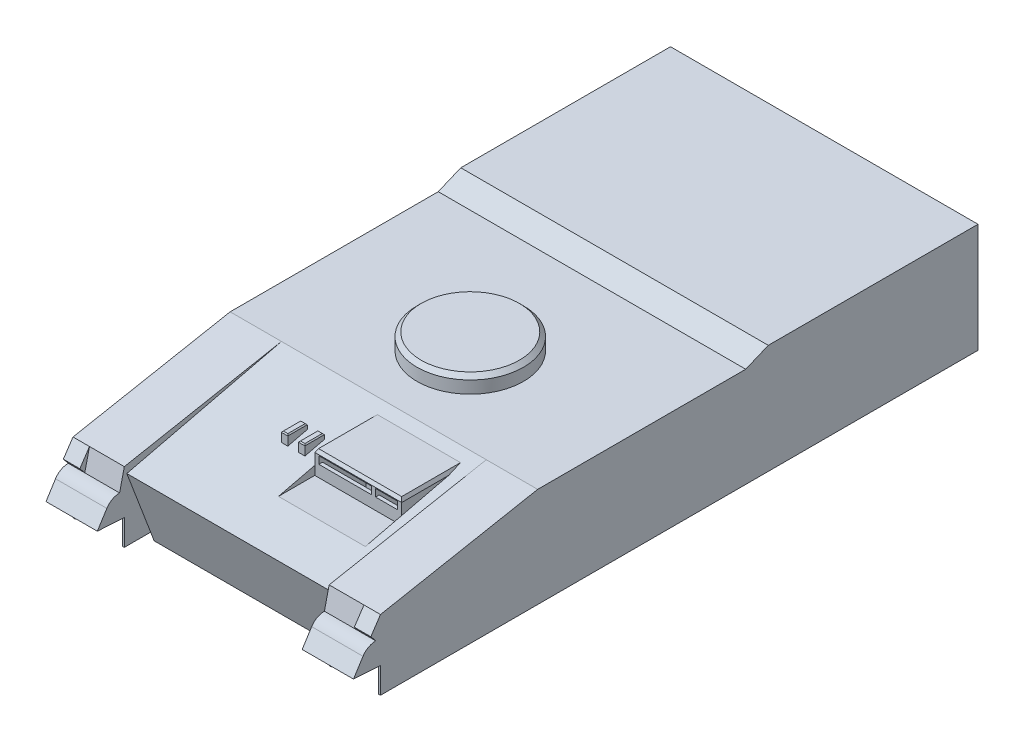
SolidWorks part; units mm, degrees
ref_plane "Front Plane" through (0, 0, 0) normal (0, 0, 1) x (1, 0, 0)
ref_plane "Top Plane" through (0, 0, 0) normal (0, 1, 0) x (1, 0, 0)
ref_plane "Right Plane" through (0, 0, 0) normal (1, 0, 0) x (0, 0, -1)
sketch "Sketch1" plane through (0, 0, 0) normal (0, 0, 1) x (1, 0, 0)
  line L1 (-266.9615, 243.5244) -> (483.6986, 243.5244)
  line L2 (-266.9615, 243.5244) -> (-266.9615, -106.3383)
  line L3 (-266.9615, -106.3383) -> (483.6986, -106.3383)
  line L4 (483.6986, 243.5244) -> (483.6986, -106.3383)
  point P0 (0, 0)
  dimension "D1" = 750.6601
extrude "Boss-Extrude1" add sketch "Sketch1" against normal blind 1265.04 and the other way blind 193.5622
ref_plane "Plane1" through (108.3686, 0, 0) normal (-1, 0, 0) x (0, 0, 1)
sketch "Sketch3" plane through (0, 243.5244, 0) normal (0, 1, 0) x (1, 0, 0)
  line L0 (148.6385, 524.5184) -> (483.6986, 524.5184)
  line L1 (-266.9615, 524.5184) -> (68.0986, 524.5184)
  line L2 (-266.9615, 1265.04) -> (-266.9615, -193.5622) construction
  line L3 (483.6986, 1265.04) -> (483.6986, -193.5622) construction
  circle A0 centre (108.3686, 400.9128) radius 130
  dimension "D1" = 260
extrude "Boss-Extrude2" add sketch "Sketch3" along normal blind 40 contours A0
sketch "Sketch5" plane through (483.6986, 0, 0) normal (1, 0, 0) x (0, 0, -1)
  line L0 (-193.5622, 170.7889) -> (190.0862, 243.5244)
  line L1 (-193.5622, -106.3383) -> (-193.5622, 243.5244) construction
  line L2 (-193.5622, 243.5244) -> (1265.04, 243.5244) construction
  line L3 (190.0862, 243.5244) -> (-193.5622, 243.5244)
  line L4 (-193.5622, 243.5244) -> (-193.5622, 170.7889)
  point P8 (94.4653, 243.5244)
  point P9 (-136.762, 199.7456)
  point P10 (-191.6549, 170.7889)
extrude "Cut-Extrude1" cut sketch "Sketch5" against normal through all
sketch "Sketch7" plane through (483.6986, 0, 0) normal (1, 0, 0) x (0, 0, -1)
  line L0 (698.0314, 243.5244) -> (753.11, 266.5226)
  line L1 (190.0862, 243.5244) -> (1265.04, 243.5244) construction
  line L2 (753.11, 266.5226) -> (1265.04, 266.5226)
  line L3 (1265.04, 243.5244) -> (1265.04, 266.5226)
  line L4 (698.0314, 243.5244) -> (1265.04, 243.5244)
  line L5 (190.0862, 243.5244) -> (1265.04, 243.5244) construction
  point P2 (694.3263, 267.5429)
  point P4 (0, 0)
  point P8 (837.0392, 270.0196)
  point P10 (769.721, 243.5244)
  point P13 (698.0314, 243.5244)
  point P14 (753.11, 266.5226)
extrude "Boss-Extrude3" add sketch "Sketch7" against normal up to surface (750.6601 mm away) up to face at (-266.9615, 89.0322, -466.6083)
chamfer "Chamfer7" distance 10 angle 45 1 edges at (108.3686, 283.5244, -270.9128)
sketch "Sketch21" plane through (-266.9615, 0, 0) normal (-1, 0, 0) x (0, 0, 1)
  line L1 (236.2193, 103.7623) -> (259.4333, 67.1114)
  line L2 (259.4333, 67.1114) -> (193.5622, 62.996)
  line L7 (193.5622, 62.996) -> (193.5622, 120.8855)
  line L8 (193.5622, 170.7889) -> (193.5622, -106.3383) construction
  line L10 (205.1048, 120.8855) -> (193.5622, 170.7889)
  line L11 (193.5622, 170.7889) -> (193.5622, 120.8855)
  arc A0 (205.1048, 120.8855) -> (236.2193, 103.7623) centre (205.1048, 84.0549) cw
  dimension "D1" = 36.8306
extrude "Boss-Extrude4" add sketch "Sketch21" against normal up to surface (750.6601 mm away) up to face at (483.6986, 139.7437, -540.5976)
sketch "Sketch20" plane through (-266.9615, 0, 0) normal (-1, 0, 0) x (0, 0, 1)
  line L0 (187.4855, 153.1852) -> (120.6339, -22.6923)
  line L1 (120.6339, -22.6923) -> (-169.8006, -69.1619)
  line L2 (193.5622, 170.7889) -> (316.2425, 170.7889)
  line L3 (-169.8006, -69.1619) -> (-1166.3691, -69.1619)
  line L4 (-1166.3691, -69.1619) -> (-1265.04, 144.9298)
  line L5 (-1265.04, 266.5226) -> (-1265.04, -106.3383) construction
  line L6 (-1265.04, 144.9298) -> (-1265.04, -106.3383)
  line L7 (-1265.04, -106.3383) -> (316.2425, -106.3383)
  line L8 (316.2425, -106.3383) -> (316.2425, 170.7889)
  line L9 (-190.0862, 243.5244) -> (187.4855, 153.1852)
  line L10 (-190.0862, 243.5244) -> (193.5622, 170.7889)
extrude "Cut-Extrude10" cut sketch "Sketch20" against normal mid plane 500 from surface at -375.3301
sketch "Sketch22" plane through (0, 0, 193.5622) normal (0, 0, 1) x (1, 0, 0)
  line L0 (-141.6314, 153.1852) -> (-141.6314, -22.6923) construction
  line L1 (-266.9615, -106.3383) -> (-141.6314, -106.3383)
  line L2 (-266.9615, -106.3383) -> (-266.9615, 0)
  line L3 (-266.9615, 0) -> (-141.6314, 0)
  line L4 (-141.6314, -106.3383) -> (-141.6314, 0)
  line L5 (-261.9615, 13.7359) -> (-266.9615, 13.7359)
  line L6 (-261.9615, 0) -> (-146.6314, 0)
  line L7 (-261.9615, 0) -> (-261.9615, 62.996)
  line L8 (-261.9615, 62.996) -> (-146.6314, 62.996)
  line L9 (-146.6314, 0) -> (-146.6314, 62.996)
  line L10 (-266.9615, 62.996) -> (-266.9615, -106.3383) construction
  line L11 (-141.6314, 62.996) -> (-266.9615, 62.996) construction
  line L13 (-146.6314, 20.3554) -> (-141.6314, 20.3554)
  line L14 (-141.6314, -106.3383) -> (-141.6314, 62.996) construction
  line L15 (108.3686, 192.4245) -> (108.3686, -192.4245) construction
  line L16 (363.3686, 20.3554) -> (358.3686, 20.3554)
  line L17 (363.3686, 0) -> (363.3686, 62.996)
  line L18 (478.6986, 62.996) -> (363.3686, 62.996)
  line L19 (478.6986, 0) -> (478.6986, 62.996)
  line L20 (478.6986, 0) -> (363.3686, 0)
  line L21 (478.6986, 13.7359) -> (483.6986, 13.7359)
  line L22 (358.3686, -106.3383) -> (358.3686, 0)
  line L23 (483.6986, 0) -> (358.3686, 0)
  line L24 (483.6986, -106.3383) -> (483.6986, 0)
  line L25 (483.6986, -106.3383) -> (358.3686, -106.3383)
  point P15 (-258.4833, 62.996)
  dimension "D1" = 5
extrude "Cut-Extrude11" cut sketch "Sketch22" against normal through all contours L3 L2 L9 | L3 L9 L8 L7 | L25 L24 L23 L20 L22 | L20 L19 L18 L17
sketch "Sketch24" plane through (0, 62.996, 0) normal (0, -1, 0) x (1, 0, 0)
  line L0 (-146.6314, -1265.04) -> (-261.9615, -1265.04) construction
  line L1 (-261.9615, 188.5622) -> (-146.6314, 188.5622)
  line L2 (-261.9615, 188.5622) -> (-261.9615, -69.9724)
  line L3 (-261.9615, -69.9724) -> (-146.6314, -69.9724)
  line L4 (-146.6314, 188.5622) -> (-146.6314, -69.9724)
  line L7 (-261.9615, -1265.04) -> (-261.9615, 193.5622) construction
  line L8 (-146.6314, -1265.04) -> (-146.6314, 193.5622) construction
  line L9 (-146.6314, 193.5622) -> (-261.9615, 193.5622) construction
  line L10 (108.3686, 192.4245) -> (108.3686, -192.4245) construction
  line L11 (363.3686, 188.5622) -> (363.3686, -69.9724)
  line L12 (478.6986, -69.9724) -> (363.3686, -69.9724)
  line L13 (478.6986, 188.5622) -> (478.6986, -69.9724)
  line L14 (478.6986, 188.5622) -> (363.3686, 188.5622)
  point P6 (-261.9615, -1258.9392)
  point P9 (-146.6314, -1257.2183)
  dimension "D1" = 1195.0675
  dimension "D2" = 5
extrude "Cut-Extrude12" cut sketch "Sketch24" against normal offset from surface (103.6518 mm away) 5
sketch "Sketch25" plane through (0, 62.996, 0) normal (0, -1, 0) x (1, 0, 0)
  line L0 (-146.6314, -1265.04) -> (-146.6314, 193.5622) construction
  line L1 (-261.9615, -69.9724) -> (-146.6314, -69.9724)
  line L2 (-261.9615, -69.9724) -> (-261.9615, -1260.04)
  line L3 (-261.9615, -1260.04) -> (-146.6314, -1260.04)
  line L4 (-146.6314, -69.9724) -> (-146.6314, -1260.04)
  line L5 (-146.6314, -1265.04) -> (-261.9615, -1265.04) construction
  line L6 (108.3686, 192.4245) -> (108.3686, -192.4245) construction
  line L7 (363.3686, -69.9724) -> (363.3686, -1260.04)
  line L8 (478.6986, -1260.04) -> (363.3686, -1260.04)
  line L9 (478.6986, -69.9724) -> (478.6986, -1260.04)
  line L10 (478.6986, -69.9724) -> (363.3686, -69.9724)
  dimension "D1" = 5
extrude "Cut-Extrude13" cut sketch "Sketch25" against normal up to vertex (152.6671 mm away)
sketch "Sketch27" plane through (0, 187.3201, 44.8189) normal (0, 0.9725, 0.2327) x (1, 0, 0)
  line L1 (330.3359, 210.3585) -> (118.2126, 210.3585)
  line L2 (330.3359, 210.3585) -> (330.3359, 57.8923)
  line L3 (330.3359, 57.8923) -> (118.2126, 57.8923)
  line L4 (118.2126, 210.3585) -> (118.2126, 57.8923)
extrude "Boss-Extrude5" add sketch "Sketch27" along direction (0, -1, 0) on the side of the normal up to surface (7.2547 mm away)
sketch "Sketch28" plane through (118.2126, 0, 0) normal (-1, 0, 0) x (0, 0, 1)
  line L1 (-159.7652, 236.2697) -> (-11.4843, 236.2697)
  line L2 (-159.7652, 236.2697) -> (-159.7652, 243.5244)
  line L3 (-159.7652, 243.5244) -> (-11.4843, 243.5244)
  line L4 (-11.4843, 236.2697) -> (-11.4843, 243.5244)
  point P4 (-159.7652, 236.2697)
  point P9 (-159.7652, 237.7759)
extrude "Cut-Extrude14" cut sketch "Sketch28" against normal up to surface (212.1233 mm away) up to face at (330.3359, 231.0275, -85.6247)
sketch "Sketch30" plane through (0, 0, -11.4843) normal (0, 0, 1) x (1, 0, 0)
  line L1 (118.2126, 200.7914) -> (330.3359, 200.7914)
  line L2 (118.2126, 200.7914) -> (118.2126, 179.5824)
  line L3 (118.2126, 179.5824) -> (330.3359, 179.5824)
  line L4 (330.3359, 200.7914) -> (330.3359, 179.5824)
extrude "Cut-Extrude15" cut sketch "Sketch30" along normal blind 115
sketch "Sketch31" plane through (0, 0, -11.4843) normal (0, 0, 1) x (1, 0, 0)
  line L0 (128.2126, 217.1263) -> (118.2126, 217.1263)
  line L1 (128.2126, 226.2697) -> (256.5256, 226.2697)
  line L2 (128.2126, 226.2697) -> (128.2126, 207.9829)
  line L3 (128.2126, 207.9829) -> (256.5256, 207.9829)
  line L4 (256.5256, 226.2697) -> (256.5256, 207.9829)
  line L5 (266.5256, 226.2697) -> (320.3359, 226.2697)
  line L6 (266.5256, 226.2697) -> (266.5256, 207.9829)
  line L7 (266.5256, 207.9829) -> (320.3359, 207.9829)
  line L8 (320.3359, 226.2697) -> (320.3359, 207.9829)
  line L9 (118.2126, 236.2697) -> (118.2126, 200.7914) construction
  line L10 (192.3691, 226.2697) -> (192.3691, 236.2697)
  line L11 (330.3359, 236.2697) -> (118.2126, 236.2697) construction
  line L12 (293.4308, 226.2697) -> (293.4308, 236.2697)
  line L13 (320.3359, 217.1263) -> (330.3359, 217.1263)
  line L14 (330.3359, 236.2697) -> (330.3359, 200.7914) construction
  line L15 (266.5256, 217.1263) -> (256.5256, 217.1263)
  dimension "D1" = 10
extrude "Cut-Extrude16" cut sketch "Sketch31" against normal blind 115 contours L4 L1 L2 L3 | L8 L5 L6 L7
sketch "Sketch32" plane through (0, 207.9829, 0) normal (0, 1, 0) x (1, 0, 0)
  line L0 (256.5256, 126.4843) -> (256.5256, 11.4843) construction
  line L1 (128.2126, 126.4843) -> (256.5256, 126.4843)
  line L2 (128.2126, 126.4843) -> (128.2126, 20.42)
  line L3 (128.2126, 20.42) -> (256.5256, 20.42)
  line L4 (256.5256, 126.4843) -> (256.5256, 20.42)
  line L5 (320.3359, 126.4843) -> (320.3359, 11.4843) construction
  line L6 (266.5256, 126.4843) -> (320.3359, 126.4843)
  line L7 (266.5256, 126.4843) -> (266.5256, 20.42)
  line L8 (266.5256, 20.42) -> (320.3359, 20.42)
  line L9 (320.3359, 126.4843) -> (320.3359, 20.42)
  point P14 (320.3359, 26.8377)
  point P15 (266.5256, 20.42)
extrude "Cut-Extrude17" cut sketch "Sketch32" against normal blind 115
sketch "Sketch34" plane through (-266.9615, 0, 0) normal (-1, 0, 0) x (0, 0, 1)
  line L0 (193.5622, 170.7889) -> (217.1467, 135.603)
  line L1 (217.1467, 135.603) -> (205.1048, 120.8855)
  line L2 (205.1048, 120.8855) -> (193.5622, 170.7889)
extrude "Boss-Extrude6" add sketch "Sketch34" against normal up to surface (750.6601 mm away) up to face at (483.6986, 140.876, -262.5148)
sketch "Sketch35" plane through (-266.9615, 0, 0) normal (-1, 0, 0) x (0, 0, 1)
  line L0 (205.1048, 120.8855) -> (193.5622, 170.7889)
  line L1 (193.5622, 170.7889) -> (217.1467, 135.603)
  line L2 (217.1467, 135.603) -> (205.1048, 120.8855)
extrude "Cut-Extrude18" cut sketch "Sketch35" against normal mid plane 670 from surface at -375.3301 starting at plane "Plane1"
chamfer "Chamfer8" distance 8 angle 30 3 edges at (330.3359, 236.2697, -85.6247) (224.2743, 236.2697, -11.4843) (118.2126, 236.2697, -85.6247)
sketch "Sketch36" plane through (0, 187.3201, 44.8189) normal (0, 0.9725, 0.2327) x (1, 0, 0)
  line L0 (118.2126, 64.2864) -> (-266.9615, 64.2864)
  line L1 (-266.9615, -148.507) -> (-266.9615, 241.5354) construction
  line L2 (46.15, 64.2864) -> (30.2472, 64.2864)
  line L3 (87.9711, 64.2864) -> (72.0682, 64.2864)
  line L4 (87.9711, 64.2864) -> (87.9711, 113.1407)
  line L5 (87.9711, 113.1407) -> (72.0682, 113.1407)
  line L6 (72.0682, 64.2864) -> (72.0682, 113.1407)
  line L11 (46.15, 64.2864) -> (46.15, 113.1407)
  line L12 (46.15, 113.1407) -> (30.2472, 113.1407)
  line L13 (30.2472, 64.2864) -> (30.2472, 113.1407)
  line L14 (46.15, 96.0849) -> (72.0682, 96.0849)
  dimension "D1" = 25.9182
extrude "Boss-Extrude7" add sketch "Sketch36" along direction (0, -1, 0) on the side of the normal offset from surface (12.6222 mm away) 10 contours L6 L0 L4 L5 | L13 L0 L11 L12
chamfer "Chamfer9" distance 2.5 angle 45 7 edges at (38.1986, 226.2697, -65.216) (46.15, 226.2697, -41.4594) (80.0197, 226.2697, -17.7028) (30.2472, 226.2697, -41.4594) (80.0197, 226.2697, -65.216) (87.9711, 226.2697, -41.4594) (72.0682, 226.2697, -41.4594)
